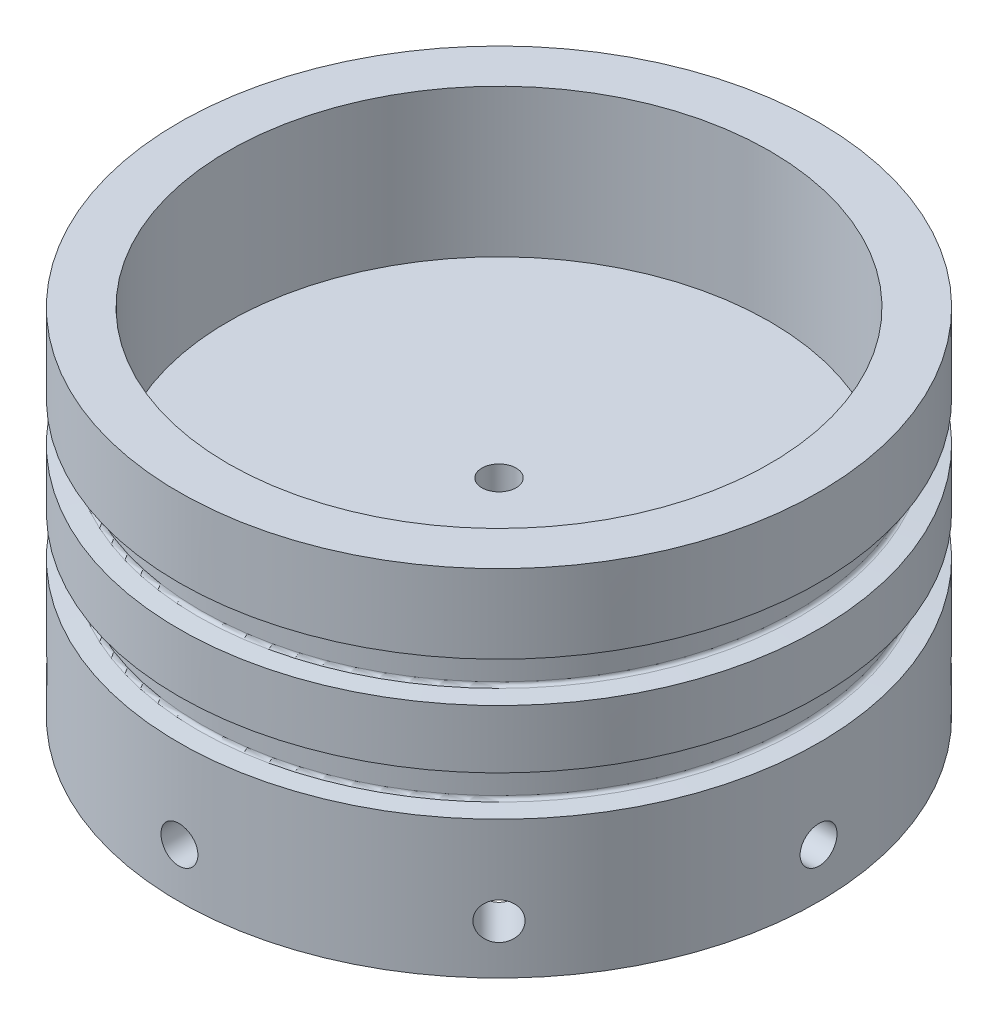
SolidWorks part; units mm, degrees
material "1060 Alloy"
ref_plane "Front Plane" through (0, 0, 0) normal (0, 0, 1) x (1, 0, 0)
ref_plane "Top Plane" through (0, 0, 0) normal (0, 1, 0) x (1, 0, 0)
ref_plane "Right Plane" through (0, 0, 0) normal (1, 0, 0) x (0, 0, -1)
sketch "Sketch1" plane through (0, 0, 0) normal (0, 0, 1) x (1, 0, 0)
  line L0 (0, 0) -> (0, 25.4) construction
  line L1 (-41.275, 13.97) -> (-41.275, 45.72)
  line L2 (-34.925, 13.97) -> (-5.1435, 13.97)
  line L3 (-2.2098, 1.4986) -> (-2.2098, 26.67)
  line L4 (-2.2098, 26.67) -> (-34.925, 26.67)
  line L5 (-34.925, 26.67) -> (-34.925, 45.72)
  line L6 (-34.925, 45.72) -> (-41.275, 45.72)
  line L7 (-41.275, 13.97) -> (-41.275, 0)
  line L8 (-3.683, 0) -> (-5.1435, 0)
  line L9 (-5.1435, 0) -> (-5.1435, 13.97)
  line L10 (-41.275, 0) -> (-34.925, 0)
  line L11 (55, 0) -> (-55, 0) construction
  line L12 (-34.925, 0) -> (-34.925, 13.97)
  line L13 (-2.2098, 1.4986) -> (-3.683, 0.0254)
  line L14 (-3.683, 0.0254) -> (-3.683, 0)
  point P10 (-2.2098, 1.4677)
  point P18 (0, 0)
  point P20 (0, 0)
  point P21 (0, 0)
  point P22 (-3.683, 0.0218)
  dimension "D1" = 2.2098
  dimension "D2" = 34.925
  dimension "D3" = 31.75
  dimension "D4" = 6.35
  dimension "D5" = 12.7
  dimension "D6" = 13.97
  dimension "D7" = 5.1435
  dimension "D8" = 135
  dimension "D9" = 3.683
  dimension "D10" = 25.1714
revolve "Revolve1" add sketch "Sketch1" angle 360 about L0
ref_plane "Plane1" through (0, 0, 0) normal (-1, 0, 0) x (0, 0, -1)
ref_plane "Plane2" through (0, 0, 0) normal (-1, 0, 0) x (0, 0, -1)
ref_plane "Plane3" through (0, 0, 0) normal (-1, 0, 0) x (0, 0, -1)
ref_plane "Plane4" through (0, 0, 0) normal (-1, 0, 0) x (0, 0, -1)
ref_plane "Plane5" through (0, 0, 0) normal (-1, 0, 0) x (0, 0, -1)
ref_plane "Plane6" through (0, 0, 0) normal (-1, 0, 0) x (0, 0, -1)
ref_plane "Plane7" through (0, 0, 0) normal (-1, 0, 0) x (0, 0, -1)
ref_plane "Plane8" through (0, 0, 0) normal (-1, 0, 0) x (0, 0, -1)
ref_plane "Plane9" through (0, 0, 0) normal (-1, 0, 0) x (0, 0, -1)
ref_plane "Plane10" through (0, 0, 0) normal (-1, 0, 0) x (0, 0, -1)
ref_plane "Plane11" through (0, 0, 0) normal (-1, 0, 0) x (0, 0, -1)
sketch "Sketch3" plane through (0, 0, 0) normal (-1, 0, 0) x (0, 0, -1)
  line L0 (38.8614, -30.6451) -> (41.3639, -30.4262)
  line L1 (41.3639, -30.4262) -> (41.3639, -35.6138)
  line L2 (41.3639, -35.6138) -> (38.8614, -35.3949)
  line L3 (38.4556, -34.9521) -> (38.4556, -31.0879)
  line L4 (0, 50) -> (0, -50) construction
  arc A0 (38.8614, -35.3949) -> (38.4556, -34.9521) centre (38.9001, -34.9521) cw
  arc A1 (38.4556, -31.0879) -> (38.8614, -30.6451) centre (38.9001, -31.0879) cw
  dimension "D4" = 0.4445
  dimension "D5" = 0.4445
  dimension "D1" = 5.1877
  dimension "D2" = 2.5025
  dimension "D3" = 3.8642
  dimension "D6" = 2.5025
  dimension "D7" = 85
  dimension "D8" = 85
  dimension "D9" = 95
revolve "Groove for AS 568-234, O-Ring1" cut sketch "Sketch3"
pattern_linear "LPattern1" count 2 spacing 12.7 along (0, -1, 0) of "Groove for AS 568-234, O-Ring1"
ref_plane "Plane12" through (0, 6.35, 0) normal (0, -1, 0) x (-1, 0, 0)
ref_axis "Axis1" through (-45.4025, 6.35, 0) along (1, 0, 0)
hole_wizard "3/16 (0.1875) Diameter Hole1" positions "3DSketch2" profile "Sketch5" hole size "3/16" standard "ANSI Inch" end condition up to next
sketch3d "3DSketch2"
  line L1 (-45.4025, 6.35, 0) -> (45.4025, 6.35, 0) construction
  point P4 (41.275, 6.35, 0)
sketch "Sketch5" plane through (41.275, 6.35, 0) normal (0, 1, 0) x (0, 0, -1)
  line L0 (0, 0) -> (0, 6.35)
  line L1 (0, 6.35) -> (2.3812, 6.35)
  line L2 (2.3812, 6.35) -> (2.3812, 0)
  line L5 (2.3812, 0) -> (0, 0)
  line L11 (0, -6.35) -> (0, 107.95) construction
  dimension "Thru Hole Dia." = 4.7625
  dimension "Thru Hole Depth" = 6.35
ref_axis "Axis2" through (0, -2.286, 0) along (0, 1, 0)
pattern_circular "CirPattern1" count 8 over 360 about axis through (0, -2.286, 0) along (0, 1, 0) of "3/16 (0.1875) Diameter Hole1"
sketch "Sketch6" plane through (0, 0, 0) normal (0, 0, 1) x (1, 0, 0)
  line L0 (0, -2.286) -> (0, 48.006) construction
  line L1 (0, -1.5396) -> (76.7104, -1.5396)
  line L2 (0, -1.5396) -> (0, 72.1727)
  line L3 (0, 72.1727) -> (76.7104, 72.1727)
  line L4 (76.7104, -1.5396) -> (76.7104, 72.1727)
revolve "Cut-Revolve1" [suppressed] cut sketch "Sketch6" angle 315 mid plane about axis through (0, -2.286, 0) along (0, 1, 0)
